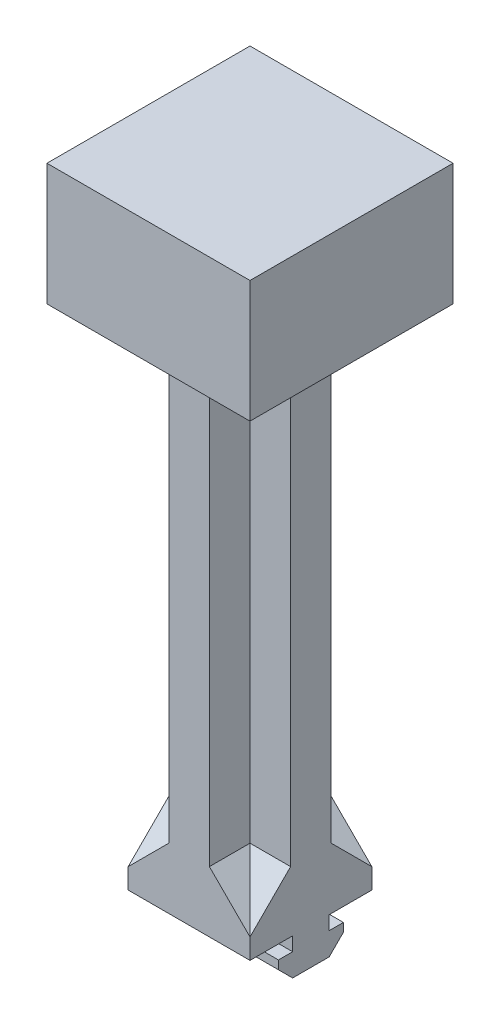
SolidWorks part; units mm, degrees
ref_plane "Front Plane" through (0, 0, 0) normal (0, 0, 1) x (1, 0, 0)
ref_plane "Top Plane" through (0, 0, 0) normal (0, 1, 0) x (1, 0, 0)
ref_plane "Right Plane" through (0, 0, 0) normal (1, 0, 0) x (0, 0, -1)
sketch "Sketch1" plane through (0, 0, 0) normal (0, 0, 1) x (1, 0, 0)
  line L1 (0, 0) -> (31.75, 0)
  line L2 (0, 0) -> (0, 19.05)
  line L3 (0, 19.05) -> (31.75, 19.05)
  line L4 (31.75, 0) -> (31.75, 19.05)
  dimension "D1" = 31.75
  dimension "D2" = 19.05
extrude "Boss-Extrude1" add sketch "Sketch1" along normal blind 31.75
shell "Shell1" thickness 3.175 removed face at (15.875, 9.525, 0)
sketch "Sketch2" plane through (0, 0, 0) normal (0, -1, 0) x (1, 0, 0)
  line L0 (12.7, 25.4) -> (12.7, 19.05)
  line L4 (12.7, 19.05) -> (6.35, 19.05)
  line L5 (6.35, 19.05) -> (6.35, 12.7)
  line L6 (6.35, 12.7) -> (12.7, 12.7)
  line L7 (12.7, 12.7) -> (12.7, 6.35)
  line L13 (12.7, 6.35) -> (19.05, 6.35)
  line L14 (19.05, 6.35) -> (19.05, 12.7)
  line L15 (19.05, 12.7) -> (25.4, 12.7)
  line L16 (25.4, 12.7) -> (25.4, 19.05)
  line L17 (25.4, 19.05) -> (19.05, 19.05)
  line L18 (19.05, 19.05) -> (19.05, 25.4)
  line L19 (19.05, 25.4) -> (12.7, 25.4)
  line L20 (0, 31.75) -> (31.75, 0) construction
  line L21 (0, 0) -> (31.75, 31.75) construction
  dimension "D1" = 6.35
extrude "Boss-Extrude2" add sketch "Sketch2" along normal blind 76.2
sketch "Sketch3" plane through (0, 0, 0) normal (1, 0, 0) x (0, 0, -1)
  line L5 (-10.795, -81.534) -> (-10.795, -82.8675)
  line L6 (-10.795, -82.8675) -> (-13.0175, -85.09)
  line L7 (-13.0175, -85.09) -> (-18.7325, -85.09)
  line L8 (-18.7325, -85.09) -> (-20.955, -82.8675)
  line L9 (-20.955, -82.8675) -> (-20.955, -81.534)
  line L14 (-6.35, -76.2) -> (-25.4, -76.2)
  line L15 (-25.4, -76.2) -> (-25.4, -79.375)
  line L16 (-25.4, -79.375) -> (-18.7325, -79.375)
  line L17 (-18.7325, -79.375) -> (-18.7325, -81.534)
  line L18 (-18.7325, -81.534) -> (-20.955, -81.534)
  line L19 (-13.0175, -79.375) -> (-13.0175, -81.534)
  line L20 (-13.0175, -81.534) -> (-10.795, -81.534)
  line L21 (-6.35, -76.2) -> (-6.35, -79.375)
  line L22 (-13.0175, -79.375) -> (-6.35, -79.375)
  line L23 (-25.4, -76.2) -> (-25.4, 0) construction
  line L24 (-19.05, -76.2) -> (-25.4, -76.2) construction
  line L26 (-6.35, -76.2) -> (-6.35, 0) construction
  point P20 (0, 0)
  dimension "D1" = 5.715
  dimension "D3" = 10.16
  dimension "D4" = 2.159
  dimension "D5" = 5.715
  dimension "D6" = 3.175
extrude "Boss-Extrude3" add sketch "Sketch3" against normal up to surface (-6.35 mm away) from surface up to face at (6.35, -38.1, 15.875) starting at face at (25.4, -38.1, 15.875)
chamfer "Chamfer1" distance 6.35 angle 45 16 edges at (9.525, -76.2, 19.05) (12.7, -76.2, 22.225) (22.225, -76.2, 19.05) (19.05, -76.2, 22.225) (22.225, -76.2, 12.7) (19.05, -76.2, 9.525) (9.525, -76.2, 12.7) (12.7, -76.2, 9.525) (12.7, 0, 22.225) (9.525, 0, 19.05) (22.225, 0, 19.05) (19.05, 0, 22.225) (19.05, 0, 9.525) (22.225, 0, 12.7) (12.7, 0, 9.525) (9.525, 0, 12.7)
